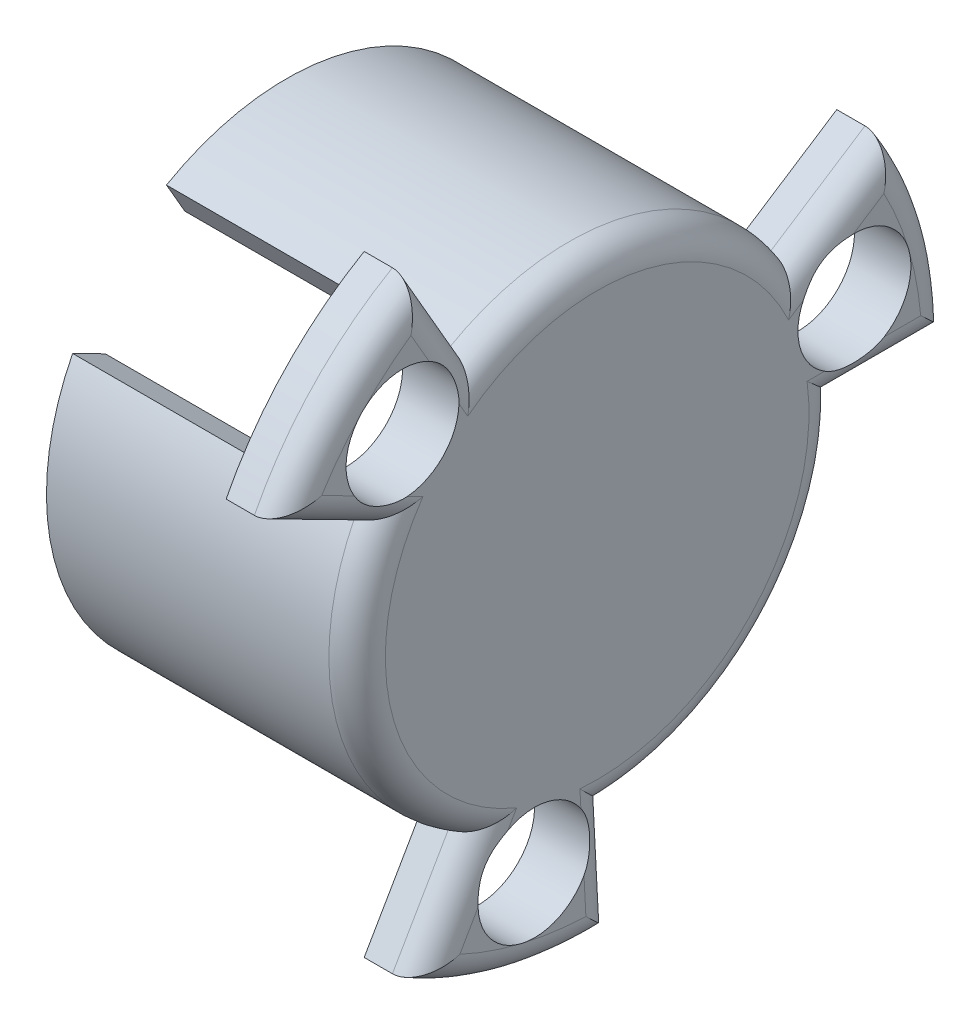
SolidWorks part; units mm, degrees
ref_plane "Front Plane" through (0, 0, 0) normal (0, 0, 1) x (1, 0, 0)
ref_plane "Top Plane" through (0, 0, 0) normal (0, 1, 0) x (1, 0, 0)
ref_plane "Right Plane" through (0, 0, 0) normal (1, 0, 0) x (0, 0, -1)
sketch "Sketch1" plane through (0, 0, 0) normal (1, 0, 0) x (0, 0, -1)
  circle A0 centre (0, 0) radius 8.5
  dimension "D1" = 17
extrude "Boss-Extrude1" add sketch "Sketch1" along normal blind 1 contours A0
sketch "Sketch2" plane through (0, 0, 0) normal (-1, 0, 0) x (0, 0, 1)
  circle A3 centre (0, 0) radius 5.375
  dimension "D1" = 10.75
extrude "Boss-Extrude2" add sketch "Sketch2" along normal blind 2 draft 40 contours A3
sketch "Sketch3" plane through (0, 0, 0) normal (-1, 0, 0) x (0, 0, 1)
  circle A2 centre (0, 0) radius 7.2
  circle A3 centre (0, 0) radius 7.2
  circle M3 centre (0, 0) radius 8.5
  dimension "D1" = 1.3
extrude "Boss-Extrude3" add sketch "Sketch3" along normal blind 10 contours A3 M3 region at (0, 0, -8.2596)
sketch "Sketch6" plane through (0, 0, 0) normal (0, 1, 0) x (1, 0, 0)
  line L1 (-10, 7.2) -> (-10, -7.2) construction
  line L4 (-10, 8.5) -> (-10, 7.2)
  line L5 (-10, 8.5) -> (-10, -8.5) construction
  line L6 (-10, 7.2) -> (-1, 7.2)
  line L8 (-1, 7.2) -> (-1, 8.5)
  line L9 (-1, 8.5) -> (-10, 8.5)
  dimension "D2" = 9
sketch "Sketch7" plane through (0, 0, 0) normal (0, 1, 0) x (1, 0, 0)
  line L0 (-10, 0) -> (1, 0) construction
  line L1 (-10, 8.5) -> (-10, -8.5) construction
  line L2 (1, -8.5) -> (1, 8.5) construction
revolve "Cut-Revolve1" cut sketch "Sketch6" angle 33 about L0
pattern_circular "CirPattern1" count 3 over 360 about axis through (1, 0, 0) along (-1, 0, 0) of "Cut-Revolve1" reverse direction yes
sketch "Sketch8" plane through (0, 0, 0) normal (0, 1, 0) x (1, 0, 0)
  line L0 (-1, 8.5) -> (1, 8.5)
  line L5 (-1, 8.5) -> (-1, 12.5)
  line L6 (-1, 12.5) -> (1, 12.5)
  line L7 (1, 12.5) -> (1, 8.5)
  dimension "D1" = 4
revolve "Revolve1" add sketch "Sketch8" angle 33 about L0
sketch "Sketch9" plane through (-1, 0, 0) normal (-1, 0, 0) x (0, 0, 1)
  line L0 (0, 0) -> (-11.9852, 3.5502) construction
  circle A0 centre (-9.1088, 2.6981) radius 2
  arc A2 (-10.4834, 6.808) -> (-12.5, 0) centre (0, 0) ccw construction
  dimension "D1" = 4
  dimension "D2" = 3
extrude "Cut-Extrude1" cut sketch "Sketch9" against normal blind 10 contours A0
pattern_circular "CirPattern3" count 3 over 360 about axis through (1, 0, 0) along (-1, 0, 0) of "Revolve1", "Cut-Extrude1"
fillet "Fillet2" radius 1 12 edges at (1, -12.1546, 2.9181) (1, 9.0933, 5.25) (1, 8.6044, 9.0672) (1, 4.7669, 9.3556) (1, -9.0933, 5.25) (1, -10.4856, -0.5495) (1, 5.7187, -8.806) (1, 0, -10.5) (1, 3.5502, -11.9852) (1, -5.851, -6.1657) (1, 8.2651, -1.9843) (1, -2.4141, 8.15)
